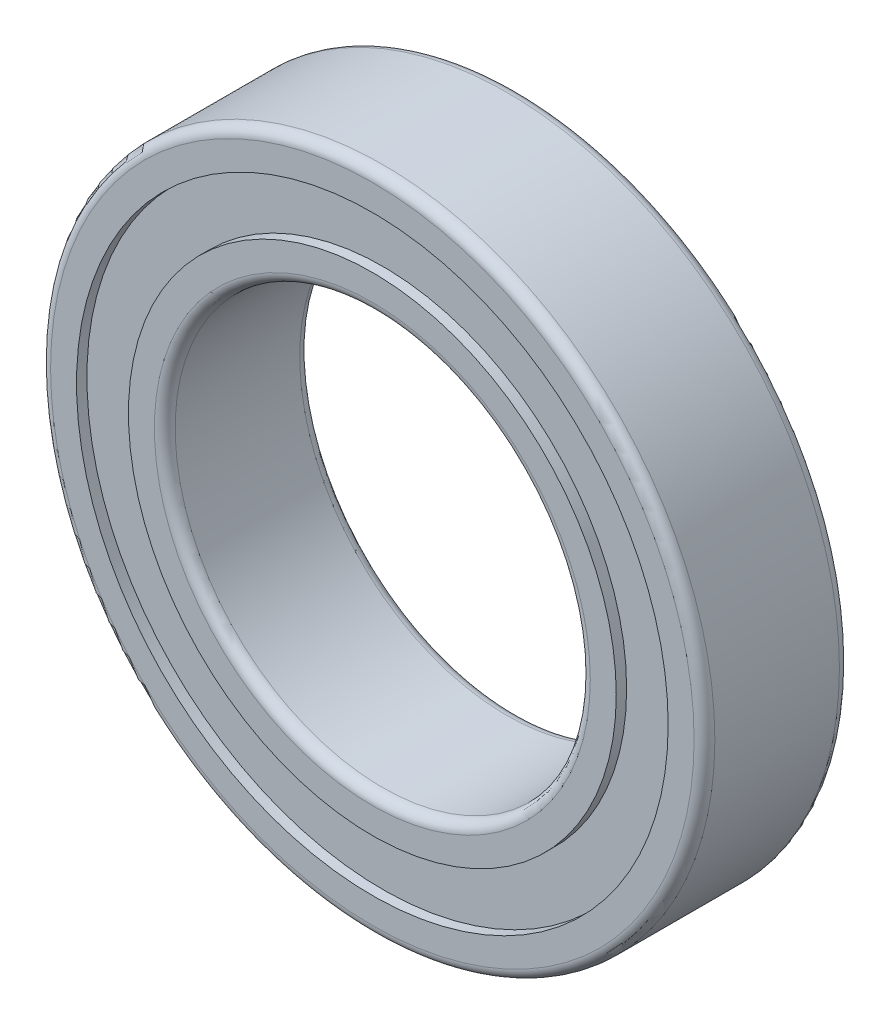
SolidWorks part; units mm, degrees
ref_plane "Front Plane" through (0, 0, 0) normal (0, 0, 1) x (1, 0, 0)
ref_plane "Top Plane" through (0, 0, 0) normal (0, 1, 0) x (1, 0, 0)
ref_plane "Right Plane" through (0, 0, 0) normal (1, 0, 0) x (0, 0, -1)
sketch "Sketch1" plane through (0, 0, 0) normal (0, 0, 1) x (1, 0, 0)
  circle A0 centre (80, 28.2573) radius 10
  circle A1 centre (80, 28.2573) radius 16
extrude "Boss-Extrude1" add sketch "Sketch1" along normal blind 7
fillet "Fillet1" radius 0.5 4 edges at (96, 28.2573, 7) (96, 28.2573, 0) (90, 28.2573, 0) (90, 28.2573, 7)
sketch "Sketch2" plane through (0, 0, 0) normal (0, 0, -1) x (-1, 0, 0)
  circle A0 centre (-80, 28.2573) radius 11.75
  circle A1 centre (-80, 28.2573) radius 14.25
extrude "Cut-Extrude1" cut sketch "Sketch2" against normal blind 0.5 contours A1 A0 region at (93.8469, 28.2573, 0)
sketch "Sketch3" plane through (0, 0, 7) normal (0, 0, 1) x (1, 0, 0)
  circle A0 centre (80, 28.2573) radius 11.75 construction
  circle A1 centre (80, 28.2573) radius 14.25
  circle A2 centre (80, 28.2573) radius 14.25
  circle A3 centre (80, 28.2573) radius 11.75
  dimension "D1" = 0
extrude "Cut-Extrude2" cut sketch "Sketch3" against normal blind 0.5
